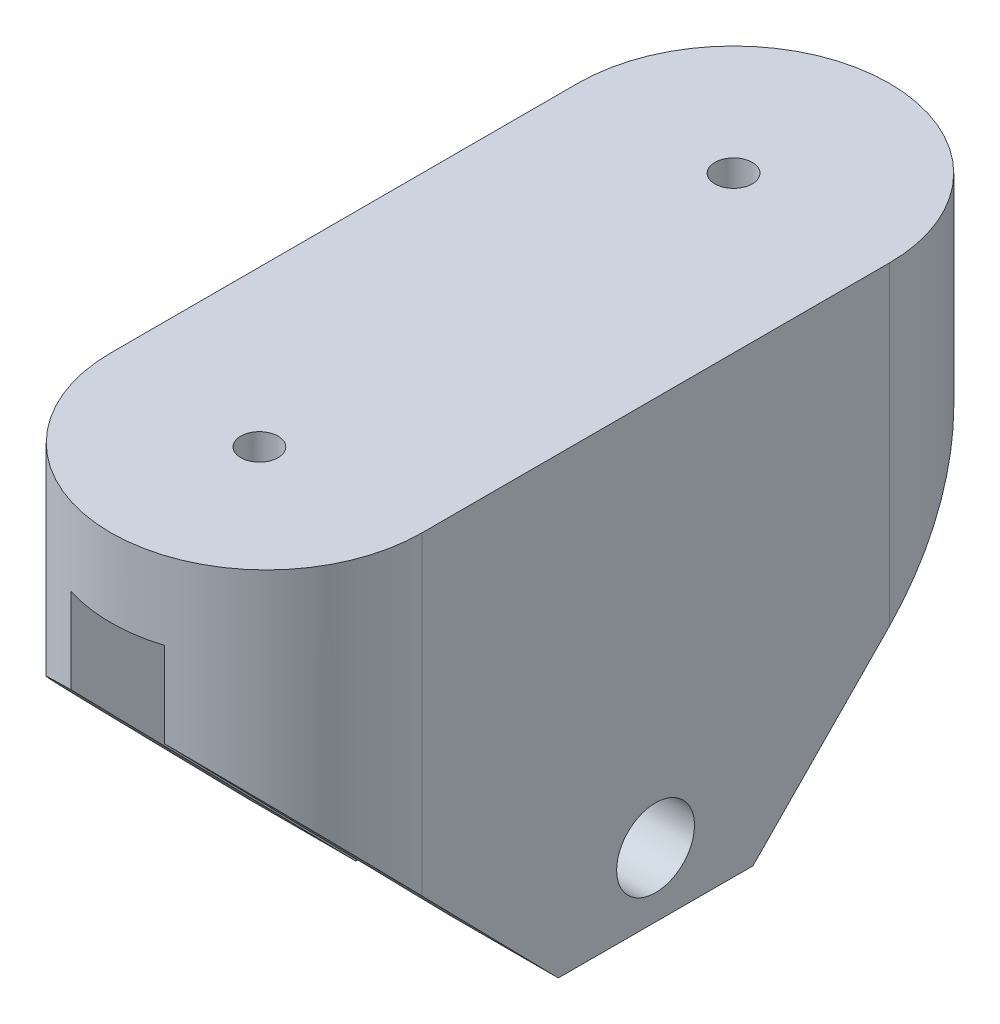
SolidWorks part; units mm, degrees
ref_plane "Front Plane" through (0, 0, 0) normal (0, 0, 1) x (1, 0, 0)
ref_plane "Top Plane" through (0, 0, 0) normal (0, 1, 0) x (1, 0, 0)
ref_plane "Right Plane" through (0, 0, 0) normal (1, 0, 0) x (0, 0, -1)
sketch "Sketch1" plane through (0, 0, 0) normal (0, 1, 0) x (1, 0, 0)
  line L0 (0, 0) -> (0, -38.1) construction
  line L1 (12.7, 0) -> (12.7, -38.1)
  line L2 (-12.7, 0) -> (-12.7, -38.1)
  line L3 (0, -35.5951) -> (-2.1693, -36.8476) construction
  line L4 (-2.1693, -36.8476) -> (-2.1693, -39.3524) construction
  line L5 (-2.1693, -39.3524) -> (0, -40.6049) construction
  line L6 (0, -40.6049) -> (2.1693, -39.3524) construction
  line L7 (2.1693, -39.3524) -> (2.1693, -36.8476) construction
  line L8 (2.1693, -36.8476) -> (0, -35.5951) construction
  line L9 (0, 3.0794) -> (-2.1693, 1.8269) construction
  line L10 (-2.1693, 1.8269) -> (-2.1693, -0.678) construction
  line L11 (-2.1693, -0.678) -> (0, -1.9304) construction
  line L12 (0, -1.9304) -> (2.1693, -0.678) construction
  line L13 (2.1693, -0.678) -> (2.1693, 1.8269) construction
  line L14 (2.1693, 1.8269) -> (0, 3.0794) construction
  arc A0 (12.7, 0) -> (-12.7, 0) centre (0, 0) ccw
  arc A1 (-12.7, -38.1) -> (12.7, -38.1) centre (0, -38.1) ccw
  circle A2 centre (0, -38.1) radius 2.1693 construction
  circle A3 centre (0, 0.5745) radius 2.1693 construction
  circle A4 centre (0, -38.1) radius 1.524 construction
  circle A5 centre (0, 0.5745) radius 1.524 construction
  point P3 (0, -19.05)
extrude "Boss-Extrude1" add sketch "Sketch1" against normal blind 6.35
sketch "Sketch2" plane through (0, 0, 0) normal (1, 0, 0) x (0, 0, -1)
  line L0 (-19.05, -6.35) -> (-19.05, -31.75) construction
  line L1 (12.7, -6.35) -> (-50.8, -6.35) construction
  line L2 (12.7, -6.35) -> (12.7, -12.7)
  line L3 (12.7, -12.7) -> (-11.1189, -37.0247)
  line L4 (-11.1189, -37.0247) -> (-26.9938, -37.0056)
  line L5 (-26.9938, -37.0056) -> (-50.8, -12.7)
  line L6 (-50.8, -12.7) -> (-50.8, -6.35)
  line L7 (-50.8, -6.35) -> (12.7, -6.35)
  circle A0 centre (-19.05, -31.75) radius 9.525 construction
extrude "Boss-Extrude3" add sketch "Sketch2" along normal through all and the other way through all
sketch "Sketch10" plane through (0, -6.35, 0) normal (0, 1, 0) x (1, 0, 0)
  line L0 (0, 0) -> (0, -38.1) construction
  line L1 (12.7, 0) -> (12.7, -38.1)
  line L2 (-12.7, 0) -> (-12.7, -38.1)
  line L3 (-12.7, 0) -> (12.7, -38.1) construction
  line L4 (12.7, -38.1) -> (0, -19.05) construction
  line L6 (-12.7, 12.7) -> (12.7, 12.7)
  line L7 (-12.7, 12.7) -> (-12.7, -50.8)
  line L8 (-12.7, -50.8) -> (12.7, -50.8)
  line L9 (12.7, 12.7) -> (12.7, -50.8)
  arc A0 (12.7, 0) -> (-12.7, 0) centre (0, 0) ccw
  arc A1 (-12.7, -38.1) -> (12.7, -38.1) centre (0, -38.1) ccw
  arc A2 (-12.7, -38.1) -> (12.7, -38.1) centre (0, -38.1) ccw construction
  arc A3 (0, -50.8) -> (12.7, -38.1) centre (0, -38.1) ccw construction
  point P2 (0, -19.05)
  arc M1 (0, 12.7) -> (12.7, 0) centre (0, 0) cw
  line M2 (12.7, 0) -> (12.7, 12.7)
  line M3 (12.7, 12.7) -> (0, 12.7)
extrude "Cut-Extrude12" cut sketch "Sketch10" against normal through all contours A0 L6 L7 | M3 M1 M2 | A1 L8 L9 | A1 L7 L8 region at (9.8632, -6.35, -9.8632) region at (9.8632, -6.35, 47.9632) region at (-9.8632, -6.35, -9.8632) region at (-9.8632, -6.35, 47.9632)
sketch "Sketch11" plane through (0, 0, 0) normal (0, 0, 1) x (1, 0, 0)
  line L0 (0, 0) -> (0, -8.3608) construction
  line L2 (0, -8.3608) -> (0, -37.0056) construction
  line L4 (12.7, -37.0056) -> (-12.7, -37.0056) construction
  line L5 (0, -37.0056) -> (0, -22.6832) construction
  line L7 (3.81, -39.0164) -> (-3.81, -39.0164)
  line L8 (3.81, -39.0164) -> (3.81, -6.35)
  line L9 (3.81, -6.35) -> (-3.81, -6.35)
  line L10 (-3.81, -39.0164) -> (-3.81, -6.35)
  line L11 (3.81, -39.0164) -> (-3.81, -6.35) construction
  line L12 (3.81, -6.35) -> (-3.81, -39.0164) construction
extrude "Cut-Extrude13" cut sketch "Sketch11" against normal through all and the other way through all
sketch "Sketch12" plane through (-12.7, 0, 0) normal (-1, 0, 0) x (0, 0, 1)
  line L0 (19.0627, -6.3691) -> (19.0627, -31.7691) construction
  line L1 (50.8127, -6.3691) -> (-12.6873, -6.3691) construction
  line L2 (50.8127, -6.3691) -> (50.8127, -12.7191) construction
  line L3 (50.8127, -12.7191) -> (26.9938, -37.0438) construction
  line L4 (26.9938, -37.0438) -> (11.1189, -37.0247) construction
  line L5 (11.1189, -37.0247) -> (-12.6873, -12.7191) construction
  line L6 (-12.6873, -12.7191) -> (-12.6873, -6.3691) construction
  line L7 (-12.6873, -6.3691) -> (50.8127, -6.3691) construction
  circle A0 centre (19.0627, -31.7691) radius 9.525 construction
  circle A1 centre (19.0627, -31.7691) radius 3.175
  point P14 (11.1189, -37.0247)
extrude "Cut-Extrude16" cut sketch "Sketch12" against normal through all
sketch "Sketch14" plane through (0, -6.35, 0) normal (0, -1, 0) x (1, 0, 0)
  line L0 (0, 2.5049) -> (-2.1693, 1.2524)
  line L1 (-2.1693, 1.2524) -> (-2.1693, -1.2524)
  line L2 (-2.1693, -1.2524) -> (0, -2.5049)
  line L3 (0, -2.5049) -> (2.1693, -1.2524)
  line L4 (2.1693, -1.2524) -> (2.1693, 1.2524)
  line L5 (2.1693, 1.2524) -> (0, 2.5049)
  line L6 (0, 41.1794) -> (-2.1693, 39.9269)
  line L7 (-2.1693, 39.9269) -> (-2.1693, 37.422)
  line L8 (-2.1693, 37.422) -> (0, 36.1696)
  line L9 (0, 36.1696) -> (2.1693, 37.422)
  line L10 (2.1693, 37.422) -> (2.1693, 39.9269)
  line L11 (2.1693, 39.9269) -> (0, 41.1794)
  circle A0 centre (0, 0) radius 2.1693 construction
  circle A1 centre (0, 38.6745) radius 2.1693 construction
  circle A2 centre (0, 0) radius 1.524 construction
  circle A3 centre (0, 38.6745) radius 1.524
extrude "Cut-Extrude17" cut sketch "Sketch14" against normal blind 2.54
sketch "Sketch15" plane through (0, 0, 0) normal (0, 1, 0) x (1, 0, 0)
  line L0 (0, -41.1794) -> (0, -36.1696) construction
  line L1 (0, -36.1696) -> (0, -2.5049) construction
  line L2 (0, -2.5049) -> (0, 2.5049) construction
  circle A0 centre (0, -38.6745) radius 1.524
  circle A1 centre (0, 0) radius 1.524
  dimension "D1" = 3.048
  dimension "D2" = 3.048
extrude "Cut-Extrude18" cut sketch "Sketch15" against normal through all
